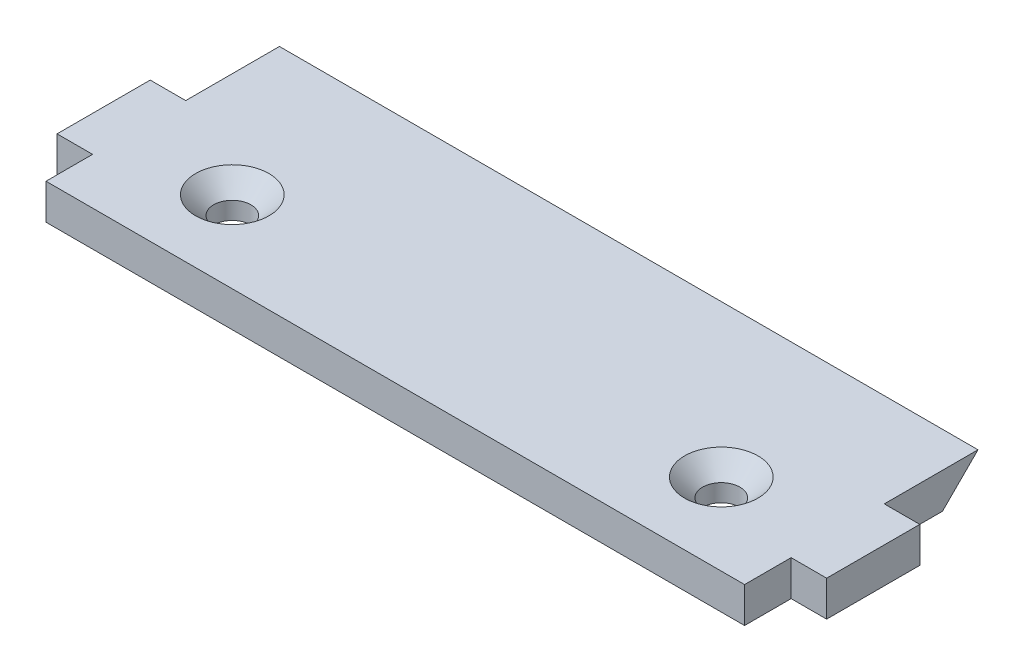
SolidWorks part; units mm, degrees
ref_plane "Front Plane" through (0, 0, 0) normal (0, 0, 1) x (1, 0, 0)
ref_plane "Top Plane" through (0, 0, 0) normal (0, 1, 0) x (1, 0, 0)
ref_plane "Right Plane" through (0, 0, 0) normal (1, 0, 0) x (0, 0, -1)
sketch "Sketch1" plane through (0, 0, 0) normal (0, 1, 0) x (1, 0, 0)
  line L0 (3.05, 12) -> (0, 7)
  line L1 (0, 0) -> (66.1, 0)
  line L2 (0, 0) -> (0, 20.05)
  line L3 (0, 20.05) -> (66.1, 20.05)
  line L4 (66.1, 0) -> (66.1, 20.05)
  line L7 (0, 12) -> (3.05, 12)
  line L8 (3.05, 20.05) -> (3.05, 12)
  line L11 (66.1, 12) -> (63.05, 12)
  line L12 (63.05, 20.05) -> (63.05, 12)
  line L13 (0, 0) -> (12.05, 0)
  line L14 (0, 0) -> (0, 7)
  line L15 (0, 7) -> (12.05, 7)
  line L16 (12.05, 0) -> (12.05, 7)
  line L17 (66.1, 0) -> (54.05, 0)
  line L18 (66.1, 0) -> (66.1, 7)
  line L19 (66.1, 7) -> (54.05, 7)
  line L20 (54.05, 0) -> (54.05, 7)
  line L21 (63.05, 12) -> (66.1, 7)
  line L23 (66.1, 0) -> (63.05, 0)
  line L24 (66.1, 0) -> (66.1, 4)
  line L25 (66.1, 4) -> (63.05, 4)
  line L26 (63.05, 0) -> (63.05, 4)
  line L27 (0, 0) -> (3.05, 0)
  line L28 (0, 0) -> (0, 4)
  line L29 (0, 4) -> (3.05, 4)
  line L30 (3.05, 0) -> (3.05, 4)
  circle A0 centre (12.05, 7) radius 1.5
  circle A1 centre (54.05, 7) radius 1.5
  dimension "D9" = 3
  dimension "D12" = 3
  dimension "D1" = 20.05
  dimension "D2" = 66.1
  dimension "D4" = 3.05
  dimension "D6" = 3.05
  dimension "D7" = 12.05
  dimension "D8" = 7
  dimension "D10" = 7
  dimension "D11" = 12.05
  dimension "D13" = 5
  dimension "D14" = 58.617
  dimension "D15" = 5
  dimension "D16" = 58.617
  dimension "D17" = 4
  dimension "D18" = 3.05
  dimension "D19" = 4
  dimension "D20" = 3.05
extrude "Boss-Extrude1" add sketch "Sketch1" along normal blind 3.05 contours L12 L3 L8 L7 L2 L1 L4 L11 | A0 L15 L2 L1 L16 | A1 L20 L1 L4 L19 | L11 L21 L4 | L7 L2 L0 region at (33.05, 0, -10.7935) region at (1.0167, 0, -10.3333) region at (6.6697, 0, -3.6881) region at (65.0833, 0, -10.3333) region at (59.4303, 0, -3.6881)
hole_wizard "CSK for M3 Flat Head Machine Screw1" positions "Sketch4" profile "Sketch5" countersink size "M3" standard "ANSI Metric" end condition through all
sketch "Sketch4" plane through (0, 3.05, 0) normal (0, 1, 0) x (1, 0, 0)
  point P0 (12.05, 7)
sketch "Sketch5" plane through (12.05, 3.05, -7) normal (1, 0, 0) x (0, 0, 1)
  line L0 (0, 0) -> (0, 3.05)
  line L1 (0, 3.05) -> (1.6, 3.05)
  line L2 (1.6, 3.05) -> (1.6, 1.55)
  line L3 (1.6, 1.55) -> (3.15, 0)
  line L5 (3.15, 0) -> (0, 0)
  line L6 (-1.6, 1.55) -> (-3.15, 0) construction
  line L11 (0, -6.35) -> (0, 107.95) construction
  dimension "Thru Hole Dia." = 3.2
  dimension "Thru Hole Depth" = 3.05
  dimension "Near C'Sink Dia." = 6.3
  dimension "Near C'Sink Angle" = 90
hole_wizard "CSK for M3 Flat Head Machine Screw2" positions "Sketch6" profile "Sketch7" countersink size "M3" standard "ANSI Metric" end condition through all
sketch "Sketch6" plane through (0, 3.05, 0) normal (0, 1, 0) x (1, 0, 0)
  point P0 (54.05, 7)
sketch "Sketch7" plane through (54.05, 3.05, -7) normal (1, 0, 0) x (0, 0, 1)
  line L0 (0, 0) -> (0, 3.05)
  line L1 (0, 3.05) -> (1.6, 3.05)
  line L2 (1.6, 3.05) -> (1.6, 1.55)
  line L3 (1.6, 1.55) -> (3.15, 0)
  line L5 (3.15, 0) -> (0, 0)
  line L6 (-1.6, 1.55) -> (-3.15, 0) construction
  line L11 (0, -6.35) -> (0, 107.95) construction
  dimension "Thru Hole Dia." = 3.2
  dimension "Thru Hole Depth" = 3.05
  dimension "Near C'Sink Dia." = 6.3
  dimension "Near C'Sink Angle" = 90
sketch "Sketch8" plane through (63.05, 0, 0) normal (1, 0, 0) x (0, 0, -1)
  line L0 (20.05, 3.05) -> (17, 0)
  line L1 (20.05, 0) -> (12, 0) construction
  line L2 (17, 0) -> (20.05, 0)
  line L3 (20.05, 0) -> (20.05, 3.05)
  dimension "D1" = 45
extrude "Cut-Extrude1" cut sketch "Sketch8" against normal through all
